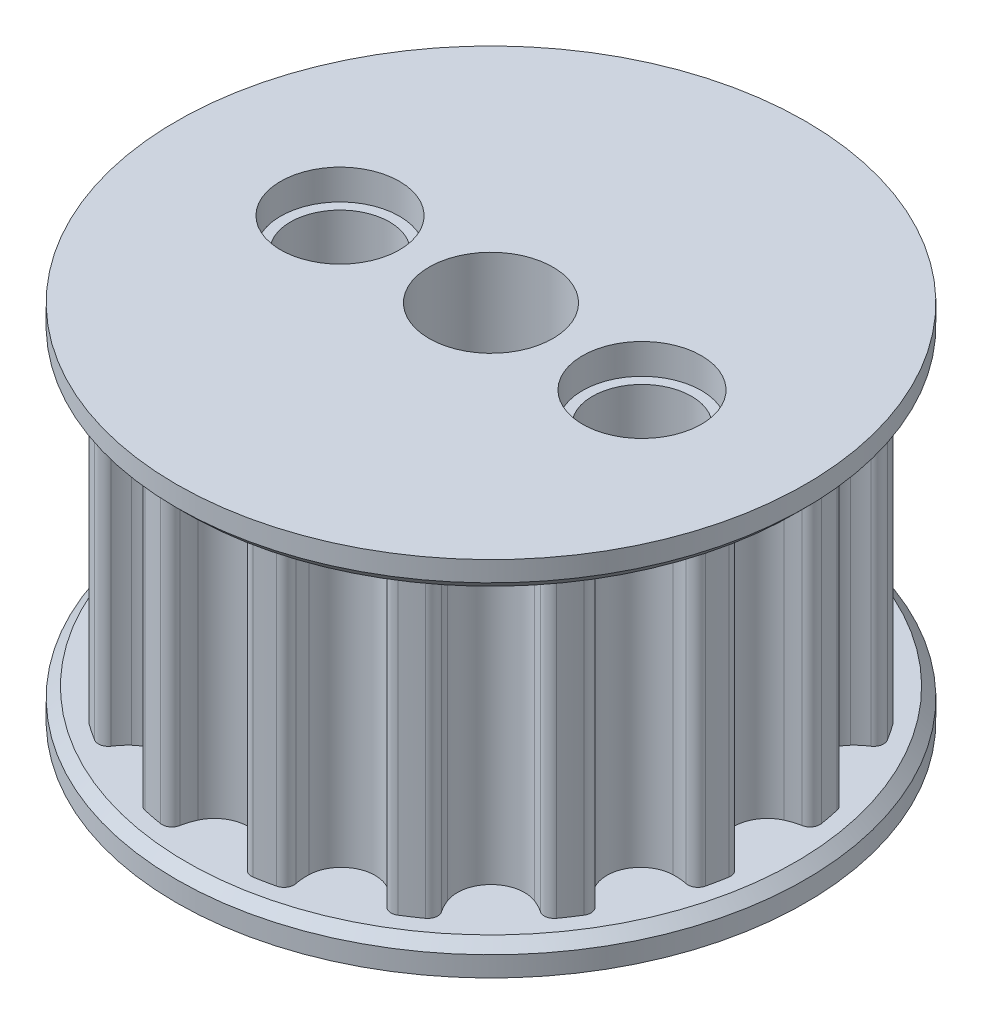
SolidWorks part; units mm, degrees
material "Alum Plate"
ref_plane "Front Plane" through (0, 0, 0) normal (0, 0, 1) x (1, 0, 0)
ref_plane "Top Plane" through (0, 0, 0) normal (0, 1, 0) x (1, 0, 0)
ref_plane "Right Plane" through (0, 0, 0) normal (1, 0, 0) x (0, 0, -1)
other "Bounding Box"
ref_plane "Default Plane" through (-8.9266, -12.7485, 0) normal (-0.1736, 0.9848, 0) x (0.9848, 0.1736, 0)
sketch "Sketch1" plane through (0, 0, 0) normal (0, 1, 0) x (1, 0, 0)
  line L0 (0, -7.8245) -> (0, 0) construction
  circle A0 centre (0, 0) radius 1.5625
  arc B0 (-1.8508, -6.777) -> (-1.6633, -7.0715) centre (-1.6061, -6.8282) ccw
  arc B1 (-1.6633, -7.0715) -> (-1.1695, -7.1697) centre (0, 0) ccw
  arc B2 (-1.1695, -7.1697) -> (-0.8836, -6.9694) centre (-1.1292, -6.923) ccw
  arc B3 (-0.7739, -6.6229) -> (-0.8836, -6.9694) centre (0.61, -7.2516) ccw
  arc B4 (0.7739, -6.6229) -> (-0.7739, -6.6229) centre (0, -6.9745) ccw
  arc B5 (0.8836, -6.9694) -> (0.7739, -6.6229) centre (-0.61, -7.2516) ccw
  arc B6 (0.8836, -6.9694) -> (1.1695, -7.1697) centre (1.1292, -6.923) ccw
  arc B7 (1.1695, -7.1697) -> (1.6633, -7.0715) centre (0, 0) ccw
  arc B8 (1.6633, -7.0715) -> (1.8508, -6.777) centre (1.6061, -6.8282) ccw
  arc B9 (1.8195, -6.4149) -> (1.8508, -6.777) centre (3.3386, -6.4662) ccw
  arc B10 (3.2495, -5.8226) -> (1.8195, -6.4149) centre (2.669, -6.4436) ccw
  arc B11 (3.4834, -6.1008) -> (3.2495, -5.8226) centre (2.2115, -6.9331) ccw
  arc B12 (3.4834, -6.1008) -> (3.8242, -6.1764) centre (3.6926, -5.9639) ccw
  arc B13 (3.8242, -6.1764) -> (4.2428, -5.8967) centre (0, 0) ccw
  arc B14 (4.2428, -5.8967) -> (4.3033, -5.5529) centre (4.0968, -5.6938) ccw
  arc B15 (4.1359, -5.2303) -> (4.3033, -5.5529) centre (5.559, -4.6963) ccw
  arc B16 (5.2303, -4.1359) -> (4.1359, -5.2303) centre (4.9317, -4.9317) ccw
  arc B17 (5.5529, -4.3033) -> (5.2303, -4.1359) centre (4.6963, -5.559) ccw
  arc B18 (5.5529, -4.3033) -> (5.8967, -4.2428) centre (5.6938, -4.0968) ccw
  arc B19 (5.8967, -4.2428) -> (6.1764, -3.8242) centre (0, 0) ccw
  arc B20 (6.1764, -3.8242) -> (6.1008, -3.4834) centre (5.9639, -3.6926) ccw
  arc B21 (5.8226, -3.2495) -> (6.1008, -3.4834) centre (6.9331, -2.2115) ccw
  arc B22 (6.4149, -1.8195) -> (5.8226, -3.2495) centre (6.4436, -2.669) ccw
  arc B23 (6.777, -1.8508) -> (6.4149, -1.8195) centre (6.4662, -3.3386) ccw
  arc B24 (6.777, -1.8508) -> (7.0715, -1.6633) centre (6.8282, -1.6061) ccw
  arc B25 (7.0715, -1.6633) -> (7.1697, -1.1695) centre (0, 0) ccw
  arc B26 (7.1697, -1.1695) -> (6.9694, -0.8836) centre (6.923, -1.1292) ccw
  arc B27 (6.6229, -0.7739) -> (6.9694, -0.8836) centre (7.2516, 0.61) ccw
  arc B28 (6.6229, 0.7739) -> (6.6229, -0.7739) centre (6.9745, 0) ccw
  arc B29 (6.9694, 0.8836) -> (6.6229, 0.7739) centre (7.2516, -0.61) ccw
  arc B30 (6.9694, 0.8836) -> (7.1697, 1.1695) centre (6.923, 1.1292) ccw
  arc B31 (7.1697, 1.1695) -> (7.0715, 1.6633) centre (0, 0) ccw
  arc B32 (7.0715, 1.6633) -> (6.777, 1.8508) centre (6.8282, 1.6061) ccw
  arc B33 (6.4149, 1.8195) -> (6.777, 1.8508) centre (6.4662, 3.3386) ccw
  arc B34 (5.8226, 3.2495) -> (6.4149, 1.8195) centre (6.4436, 2.669) ccw
  arc B35 (6.1008, 3.4834) -> (5.8226, 3.2495) centre (6.9331, 2.2115) ccw
  arc B36 (6.1008, 3.4834) -> (6.1764, 3.8242) centre (5.9639, 3.6926) ccw
  arc B37 (6.1764, 3.8242) -> (5.8967, 4.2428) centre (0, 0) ccw
  arc B38 (5.8967, 4.2428) -> (5.5529, 4.3033) centre (5.6938, 4.0968) ccw
  arc B39 (5.2303, 4.1359) -> (5.5529, 4.3033) centre (4.6963, 5.559) ccw
  arc B40 (4.1359, 5.2303) -> (5.2303, 4.1359) centre (4.9317, 4.9317) ccw
  arc B41 (4.3033, 5.5529) -> (4.1359, 5.2303) centre (5.559, 4.6963) ccw
  arc B42 (4.3033, 5.5529) -> (4.2428, 5.8967) centre (4.0968, 5.6938) ccw
  arc B43 (4.2428, 5.8967) -> (3.8242, 6.1764) centre (0, 0) ccw
  arc B44 (3.8242, 6.1764) -> (3.4834, 6.1008) centre (3.6926, 5.9639) ccw
  arc B45 (3.2495, 5.8226) -> (3.4834, 6.1008) centre (2.2115, 6.9331) ccw
  arc B46 (1.8195, 6.4149) -> (3.2495, 5.8226) centre (2.669, 6.4436) ccw
  arc B47 (1.8508, 6.777) -> (1.8195, 6.4149) centre (3.3386, 6.4662) ccw
  arc B48 (1.8508, 6.777) -> (1.6633, 7.0715) centre (1.6061, 6.8282) ccw
  arc B49 (1.6633, 7.0715) -> (1.1695, 7.1697) centre (0, 0) ccw
  arc B50 (1.1695, 7.1697) -> (0.8836, 6.9694) centre (1.1292, 6.923) ccw
  arc B51 (0.7739, 6.6229) -> (0.8836, 6.9694) centre (-0.61, 7.2516) ccw
  arc B52 (-0.7739, 6.6229) -> (0.7739, 6.6229) centre (0, 6.9745) ccw
  arc B53 (-0.8836, 6.9694) -> (-0.7739, 6.6229) centre (0.61, 7.2516) ccw
  arc B54 (-0.8836, 6.9694) -> (-1.1695, 7.1697) centre (-1.1292, 6.923) ccw
  arc B55 (-1.1695, 7.1697) -> (-1.6633, 7.0715) centre (0, 0) ccw
  arc B56 (-1.6633, 7.0715) -> (-1.8508, 6.777) centre (-1.6061, 6.8282) ccw
  arc B57 (-1.8195, 6.4149) -> (-1.8508, 6.777) centre (-3.3386, 6.4662) ccw
  arc B58 (-3.2495, 5.8226) -> (-1.8195, 6.4149) centre (-2.669, 6.4436) ccw
  arc B59 (-3.4834, 6.1008) -> (-3.2495, 5.8226) centre (-2.2115, 6.9331) ccw
  arc B60 (-3.4834, 6.1008) -> (-3.8242, 6.1764) centre (-3.6926, 5.9639) ccw
  arc B61 (-3.8242, 6.1764) -> (-4.2428, 5.8967) centre (0, 0) ccw
  arc B62 (-4.2428, 5.8967) -> (-4.3033, 5.5529) centre (-4.0968, 5.6938) ccw
  arc B63 (-4.1359, 5.2303) -> (-4.3033, 5.5529) centre (-5.559, 4.6963) ccw
  arc B64 (-5.2303, 4.1359) -> (-4.1359, 5.2303) centre (-4.9317, 4.9317) ccw
  arc B65 (-5.5529, 4.3033) -> (-5.2303, 4.1359) centre (-4.6963, 5.559) ccw
  arc B66 (-5.5529, 4.3033) -> (-5.8967, 4.2428) centre (-5.6938, 4.0968) ccw
  arc B67 (-5.8967, 4.2428) -> (-6.1764, 3.8242) centre (0, 0) ccw
  arc B68 (-6.1764, 3.8242) -> (-6.1008, 3.4834) centre (-5.9639, 3.6926) ccw
  arc B69 (-5.8226, 3.2495) -> (-6.1008, 3.4834) centre (-6.9331, 2.2115) ccw
  arc B70 (-6.4149, 1.8195) -> (-5.8226, 3.2495) centre (-6.4436, 2.669) ccw
  arc B71 (-6.777, 1.8508) -> (-6.4149, 1.8195) centre (-6.4662, 3.3386) ccw
  arc B72 (-6.777, 1.8508) -> (-7.0715, 1.6633) centre (-6.8282, 1.6061) ccw
  arc B73 (-7.0715, 1.6633) -> (-7.1697, 1.1695) centre (0, 0) ccw
  arc B74 (-7.1697, 1.1695) -> (-6.9694, 0.8836) centre (-6.923, 1.1292) ccw
  arc B75 (-6.6229, 0.7739) -> (-6.9694, 0.8836) centre (-7.2516, -0.61) ccw
  arc B76 (-6.6229, -0.7739) -> (-6.6229, 0.7739) centre (-6.9745, 0) ccw
  arc B77 (-6.9694, -0.8836) -> (-6.6229, -0.7739) centre (-7.2516, 0.61) ccw
  arc B78 (-6.9694, -0.8836) -> (-7.1697, -1.1695) centre (-6.923, -1.1292) ccw
  arc B79 (-7.1697, -1.1695) -> (-7.0715, -1.6633) centre (0, 0) ccw
  arc B80 (-7.0715, -1.6633) -> (-6.777, -1.8508) centre (-6.8282, -1.6061) ccw
  arc B81 (-6.4149, -1.8195) -> (-6.777, -1.8508) centre (-6.4662, -3.3386) ccw
  arc B82 (-5.8226, -3.2495) -> (-6.4149, -1.8195) centre (-6.4436, -2.669) ccw
  arc B83 (-6.1008, -3.4834) -> (-5.8226, -3.2495) centre (-6.9331, -2.2115) ccw
  arc B84 (-6.1008, -3.4834) -> (-6.1764, -3.8242) centre (-5.9639, -3.6926) ccw
  arc B85 (-6.1764, -3.8242) -> (-5.8967, -4.2428) centre (0, 0) ccw
  arc B86 (-5.8967, -4.2428) -> (-5.5529, -4.3033) centre (-5.6938, -4.0968) ccw
  arc B87 (-5.2303, -4.1359) -> (-5.5529, -4.3033) centre (-4.6963, -5.559) ccw
  arc B88 (-4.1359, -5.2303) -> (-5.2303, -4.1359) centre (-4.9317, -4.9317) ccw
  arc B89 (-4.3033, -5.5529) -> (-4.1359, -5.2303) centre (-5.559, -4.6963) ccw
  arc B90 (-4.3033, -5.5529) -> (-4.2428, -5.8967) centre (-4.0968, -5.6938) ccw
  arc B91 (-4.2428, -5.8967) -> (-3.8242, -6.1764) centre (0, 0) ccw
  arc B92 (-3.8242, -6.1764) -> (-3.4834, -6.1008) centre (-3.6926, -5.9639) ccw
  arc B93 (-3.2495, -5.8226) -> (-3.4834, -6.1008) centre (-2.2115, -6.9331) ccw
  arc B94 (-1.8195, -6.4149) -> (-3.2495, -5.8226) centre (-2.669, -6.4436) ccw
  arc B95 (-1.8508, -6.777) -> (-1.8195, -6.4149) centre (-3.3386, -6.4662) ccw
  dimension "D1" = 3.125
sketch_block_instance "Block-GT2 16 Tooth Profile-1"
sketch_block "Block-GT2 16 Tooth Profile"
extrude "Boss-Extrude1" add sketch "Sketch1" along normal mid plane 7.62
sketch "Sketch2" plane through (0, -3.81, 0) normal (0, -1, 0) x (1, 0, 0)
  circle A0 centre (0, 0) radius 7.9375
  circle A1 centre (0, 0) radius 1.5625 construction
  circle A2 centre (0, 0) radius 1.5625
  dimension "D1" = 15.875
extrude "Boss-Extrude2" add sketch "Sketch2" along normal blind 0.762 separate body
sketch "Sketch3" plane through (0, -4.572, 0) normal (0, -1, 0) x (1, 0, 0)
  line L0 (0, 0) -> (3.81, 0) construction
  line L1 (0, 0) -> (-3.81, 0) construction
  circle A0 centre (-3.81, 0) radius 1.5
  circle A1 centre (3.81, 0) radius 1.5
  dimension "D1" = 3
  dimension "D2" = 3.81
extrude "Cut-Extrude1" cut sketch "Sketch3" against normal through all
sketch "Sketch4" plane through (0, -3.81, 0) normal (0, -1, 0) x (1, 0, 0)
  circle A0 centre (-3.81, 0) radius 1.25
  circle A1 centre (3.81, 0) radius 1.25
  dimension "D1" = 2.5
extrude "Cut-Extrude2" cut sketch "Sketch4" against normal through all
chamfer "Chamfer1" distance 0.254 angle 45 1 edges at (0, -3.81, -7.9375)
mirror "Mirror2" about plane through (0, 0, 0) normal (0, 1, 0) of bodies 107 105
combine bodies "Combine1" operation type add bodies to combine 106 108 107
